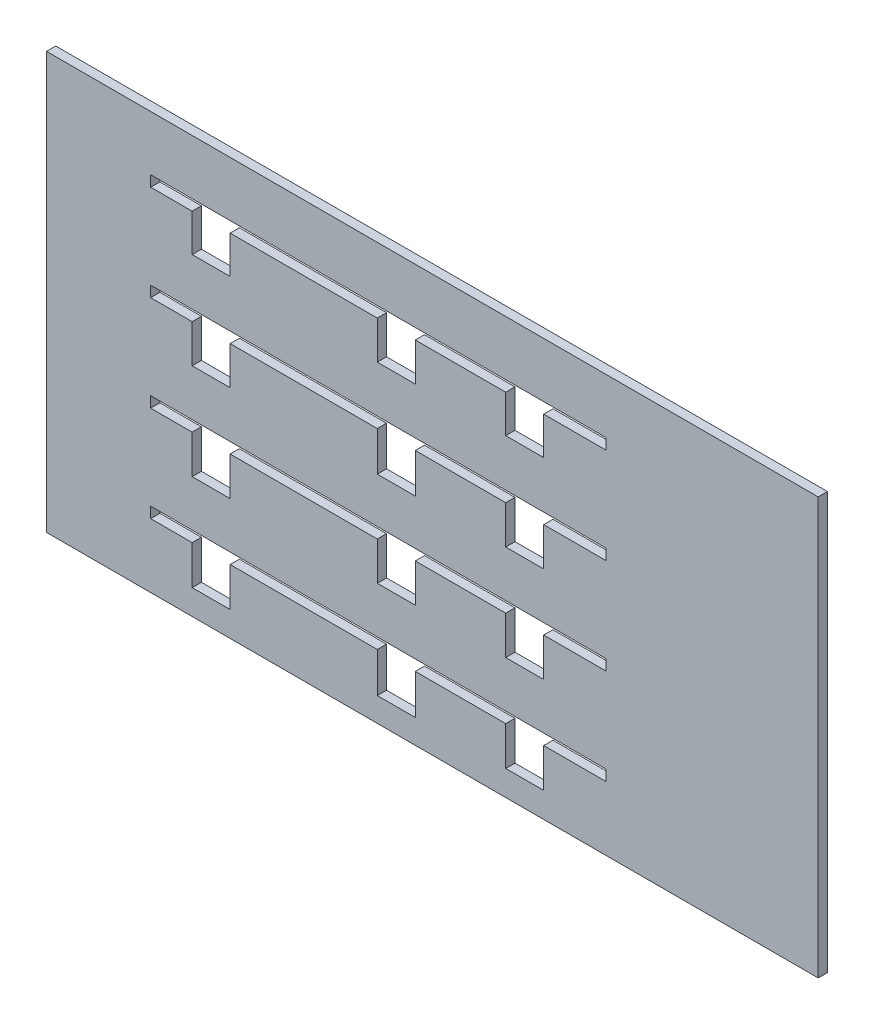
SolidWorks part; units mm, degrees
ref_plane "Front Plane" through (0, 0, 0) normal (0, 0, 1) x (1, 0, 0)
ref_plane "Top Plane" through (0, 0, 0) normal (0, 1, 0) x (1, 0, 0)
ref_plane "Right Plane" through (0, 0, 0) normal (1, 0, 0) x (0, 0, -1)
sketch "Sketch1" plane through (0, 0, 0) normal (0, 0, 1) x (1, 0, 0)
  line L2 (79.894, 76.2298) -> (148.894, 76.2298)
  line L6 (79.894, -58.7702) -> (148.894, -58.7702)
  line L7 (148.894, 76.2298) -> (148.894, -58.7702)
  line L11 (-67.1671, 76.2298) -> (79.894, 76.2298)
  line L15 (-67.1671, -58.7702) -> (79.894, -58.7702)
  line L17 (-67.1671, 76.2298) -> (-72.1671, 76.2298)
  line L19 (-67.1671, -58.7702) -> (-72.1671, -58.7702)
  line L21 (-72.1671, 76.2298) -> (-98.1671, 76.2298)
  line L23 (-72.1671, -58.7702) -> (-98.1671, -58.7702)
  line L25 (-98.1671, 76.2298) -> (-101.1671, 76.2298)
  line L27 (-98.1671, -58.7702) -> (-101.1671, -58.7702)
  line L28 (-101.1671, 76.2298) -> (-101.1671, -58.7702)
extrude "Boss-Extrude1" add sketch "Sketch1" against normal blind 3 contours L21 L25 L28 L27 L23 L19 L15 L6 L7 L2 L11 L17
sketch "Sketch3" plane through (0, 0, 0) normal (0, 0, 1) x (1, 0, 0)
  line L0 (-67.1671, -37.7702) -> (79.8329, -37.7702) construction
  line L1 (-67.1671, 58.2298) -> (79.8329, 58.2298)
  line L2 (-67.1671, 58.2298) -> (-67.1671, 55.2298)
  line L3 (-67.1671, 55.2298) -> (79.8329, 55.2298)
  line L4 (79.8329, 58.2298) -> (79.8329, 55.2298)
  line L5 (-67.1671, 27.2298) -> (79.8329, 27.2298)
  line L6 (-67.1671, 27.2298) -> (-67.1671, 24.2298)
  line L7 (-67.1671, 24.2298) -> (79.8329, 24.2298)
  line L8 (79.8329, 27.2298) -> (79.8329, 24.2298)
  line L9 (-67.1671, -3.7702) -> (79.8329, -3.7702)
  line L10 (-67.1671, -3.7702) -> (-67.1671, -6.7702)
  line L11 (-67.1671, -6.7702) -> (79.8329, -6.7702)
  line L12 (79.8329, -3.7702) -> (79.8329, -6.7702)
  line L13 (-67.1671, -34.7702) -> (79.8329, -34.7702)
  line L14 (-67.1671, -34.7702) -> (-67.1671, -37.7702)
  line L15 (-67.1671, -37.7702) -> (79.8329, -37.7702)
  line L16 (79.8329, -34.7702) -> (79.8329, -37.7702)
  line L17 (-67.4171, 58.4798) -> (80.0829, 58.4798)
  line L18 (80.0829, 58.4798) -> (80.0829, 54.9798)
  line L19 (-67.4171, 54.9798) -> (80.0829, 54.9798)
  line L20 (-67.4171, 58.4798) -> (-67.4171, 54.9798)
  line L21 (-67.4171, 27.4798) -> (80.0829, 27.4798)
  line L22 (80.0829, 27.4798) -> (80.0829, 23.9798)
  line L23 (-67.4171, 23.9798) -> (80.0829, 23.9798)
  line L24 (-67.4171, 27.4798) -> (-67.4171, 23.9798)
  line L25 (-67.4171, -3.5202) -> (80.0829, -3.5202)
  line L26 (80.0829, -3.5202) -> (80.0829, -7.0202)
  line L27 (-67.4171, -7.0202) -> (80.0829, -7.0202)
  line L28 (-67.4171, -3.5202) -> (-67.4171, -7.0202)
  line L29 (-67.4171, -34.5202) -> (80.0829, -34.5202)
  line L30 (80.0829, -34.5202) -> (80.0829, -38.0202)
  line L31 (-67.4171, -38.0202) -> (80.0829, -38.0202)
  line L32 (-67.4171, -34.5202) -> (-67.4171, -38.0202)
  dimension "D1" = 0.25
extrude "Cut-Extrude2" cut sketch "Sketch3" against normal blind 3
sketch "Sketch5" plane through (0, 0, 0) normal (0, 0, 1) x (1, 0, 0)
  line L0 (-67.4171, 58.4798) -> (-67.4171, 48.9298)
  line L1 (-67.4171, 48.9298) -> (-47.8171, 48.9298)
  line L2 (-47.8171, 48.9298) -> (12.1729, 48.9298)
  line L3 (12.1729, 48.9298) -> (53.7829, 48.9298)
  line L4 (-67.4171, 17.8298) -> (-47.8171, 17.8298)
  line L5 (-67.4171, 27.4298) -> (-67.4171, 17.8298)
  line L6 (-47.8171, 17.8298) -> (12.1729, 17.8298)
  line L7 (12.1729, 17.8298) -> (53.7829, 17.8298)
  line L8 (-47.8171, -13.1702) -> (12.1729, -13.1702)
  line L9 (-67.4171, -13.1702) -> (-47.8171, -13.1702)
  line L10 (12.1729, -13.1702) -> (53.7829, -13.1702)
  line L11 (-67.4171, -3.5702) -> (-67.4171, -13.1702)
  line L12 (12.1729, -44.1702) -> (53.7829, -44.1702)
  line L13 (-67.4171, -44.1702) -> (-47.8171, -44.1702)
  line L14 (-67.4171, -34.5702) -> (-67.4171, -44.1702)
  line L15 (-47.8171, -44.1702) -> (12.1729, -44.1702)
  line L16 (-53.9671, 42.8084) -> (-41.6671, 42.8084)
  line L17 (-53.9671, 42.8084) -> (-53.9671, 55.0511)
  line L18 (-41.6671, 42.8084) -> (-41.6671, 55.0511)
  line L19 (-53.9671, 55.0511) -> (-41.6671, 55.0511)
  line L20 (-53.9671, 42.8084) -> (-41.6671, 55.0511) construction
  line L21 (-41.6671, 42.8084) -> (-53.9671, 55.0511) construction
  line L22 (6.0229, 42.6113) -> (18.3229, 42.6113)
  line L23 (6.0229, 42.6113) -> (6.0229, 55.2482)
  line L24 (18.3229, 42.6113) -> (18.3229, 55.2482)
  line L25 (6.0229, 55.2482) -> (18.3229, 55.2482)
  line L26 (6.0229, 42.6113) -> (18.3229, 55.2482) construction
  line L27 (18.3229, 42.6113) -> (6.0229, 55.2482) construction
  line L28 (47.6329, 42.786) -> (59.9329, 42.786)
  line L29 (47.6329, 42.786) -> (47.6329, 55.0735)
  line L30 (59.9329, 42.786) -> (59.9329, 55.0735)
  line L31 (47.6329, 55.0735) -> (59.9329, 55.0735)
  line L32 (47.6329, 42.786) -> (59.9329, 55.0735) construction
  line L33 (59.9329, 42.786) -> (47.6329, 55.0735) construction
  line L34 (-53.9671, 11.5936) -> (-41.6671, 11.5936)
  line L35 (-53.9671, 11.5936) -> (-53.9671, 24.0659)
  line L36 (-41.6671, 11.5936) -> (-41.6671, 24.0659)
  line L37 (-53.9671, 24.0659) -> (-41.6671, 24.0659)
  line L38 (-53.9671, 11.5936) -> (-41.6671, 24.0659) construction
  line L39 (-41.6671, 11.5936) -> (-53.9671, 24.0659) construction
  line L40 (6.0229, 11.1777) -> (18.3229, 11.1777)
  line L41 (6.0229, 11.1777) -> (6.0229, 24.4819)
  line L42 (18.3229, 11.1777) -> (18.3229, 24.4819)
  line L43 (6.0229, 24.4819) -> (18.3229, 24.4819)
  line L44 (6.0229, 11.1777) -> (18.3229, 24.4819) construction
  line L45 (18.3229, 11.1777) -> (6.0229, 24.4819) construction
  line L46 (47.6329, 11.5365) -> (59.9329, 11.5365)
  line L47 (47.6329, 11.5365) -> (47.6329, 24.123)
  line L48 (59.9329, 11.5365) -> (59.9329, 24.123)
  line L49 (47.6329, 24.123) -> (59.9329, 24.123)
  line L50 (47.6329, 11.5365) -> (59.9329, 24.123) construction
  line L51 (59.9329, 11.5365) -> (47.6329, 24.123) construction
  line L52 (-53.9671, -19.5185) -> (-41.6671, -19.5185)
  line L53 (-53.9671, -19.5185) -> (-53.9671, -6.8219)
  line L54 (-41.6671, -19.5185) -> (-41.6671, -6.8219)
  line L55 (-53.9671, -6.8219) -> (-41.6671, -6.8219)
  line L56 (-53.9671, -19.5185) -> (-41.6671, -6.8219) construction
  line L57 (-41.6671, -19.5185) -> (-53.9671, -6.8219) construction
  line L58 (6.0229, -19.4399) -> (18.3229, -19.4399)
  line L59 (6.0229, -19.4399) -> (6.0229, -6.9005)
  line L60 (18.3229, -19.4399) -> (18.3229, -6.9005)
  line L61 (6.0229, -6.9005) -> (18.3229, -6.9005)
  line L62 (6.0229, -19.4399) -> (18.3229, -6.9005) construction
  line L63 (18.3229, -19.4399) -> (6.0229, -6.9005) construction
  line L64 (47.6329, -19.4836) -> (59.9329, -19.4836)
  line L65 (47.6329, -19.4836) -> (47.6329, -6.8568)
  line L66 (59.9329, -19.4836) -> (59.9329, -6.8568)
  line L67 (47.6329, -6.8568) -> (59.9329, -6.8568)
  line L68 (47.6329, -19.4836) -> (59.9329, -6.8568) construction
  line L69 (59.9329, -19.4836) -> (47.6329, -6.8568) construction
  line L70 (47.6329, -50.6021) -> (59.9329, -50.6021)
  line L71 (47.6329, -50.6021) -> (47.6329, -37.7383)
  line L72 (59.9329, -50.6021) -> (59.9329, -37.7383)
  line L73 (47.6329, -37.7383) -> (59.9329, -37.7383)
  line L74 (47.6329, -50.6021) -> (59.9329, -37.7383) construction
  line L75 (59.9329, -50.6021) -> (47.6329, -37.7383) construction
  line L76 (6.0229, -50.9562) -> (18.3229, -50.9562)
  line L77 (6.0229, -50.9562) -> (6.0229, -37.3843)
  line L78 (18.3229, -50.9562) -> (18.3229, -37.3843)
  line L79 (6.0229, -37.3843) -> (18.3229, -37.3843)
  line L80 (6.0229, -50.9562) -> (18.3229, -37.3843) construction
  line L81 (18.3229, -50.9562) -> (6.0229, -37.3843) construction
  line L82 (-53.9671, -50.6562) -> (-41.6671, -50.6562)
  line L83 (-53.9671, -50.6562) -> (-53.9671, -37.6843)
  line L84 (-41.6671, -50.6562) -> (-41.6671, -37.6843)
  line L85 (-53.9671, -37.6843) -> (-41.6671, -37.6843)
  line L86 (-53.9671, -50.6562) -> (-41.6671, -37.6843) construction
  line L87 (-41.6671, -50.6562) -> (-53.9671, -37.6843) construction
  circle A0 centre (-47.8171, 48.9298) radius 6.15
  circle A1 centre (12.1729, 48.9298) radius 6.15
  circle A2 centre (53.7829, 48.9298) radius 6.15
  circle A3 centre (12.1729, 17.8298) radius 6.15
  circle A4 centre (53.7829, 17.8298) radius 6.15
  circle A5 centre (-47.8171, 17.8298) radius 6.15
  circle A6 centre (-47.8171, -13.1702) radius 6.15
  circle A7 centre (53.7829, -13.1702) radius 6.15
  circle A8 centre (12.1729, -13.1702) radius 6.15
  circle A9 centre (12.1729, -44.1702) radius 6.15
  circle A10 centre (53.7829, -44.1702) radius 6.15
  circle A11 centre (-47.8171, -44.1702) radius 6.15
  point P33 (0, 0)
  point P34 (0, 0)
  point P55 (0, 0)
  point P84 (0, 0)
  dimension "D1" = 19.6
  dimension "D2" = 59.99
  dimension "D3" = 41.61
  dimension "D4" = 9.55
  dimension "D5" = 9.6
  dimension "D6" = 9.6
  dimension "D7" = 9.6
extrude "Cut-Extrude8" cut sketch "Sketch5" against normal blind 10 contours L84 L85 L83 L82 | L77 L79 L78 L76 | L71 L73 L72 L70 | L64 L66 L67 L65 | L58 L60 L61 L59 | L52 L54 L55 L53 | L34 L36 L37 L35 | L40 L42 L43 L41 | L46 L48 L49 L47 | L28 L30 L31 L29 | L22 L24 L25 L23 | L16 L18 L19 L17
